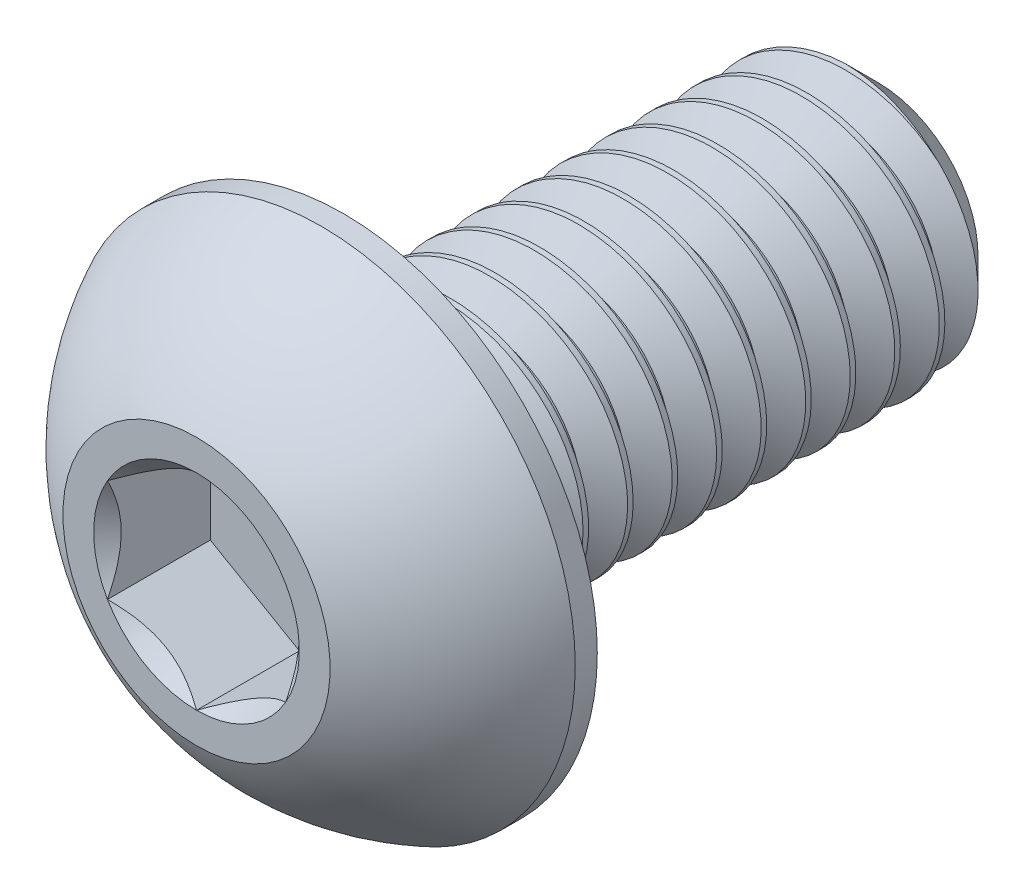
SolidWorks part; units mm, degrees
note: '?' marks a value the reader was unsure of.
ref_plane "Front" through (0, 0, 0) normal (0, 0, 1) x (1, 0, 0)
ref_plane "Top" through (0, 0, 0) normal (0, 1, 0) x (1, 0, 0)
ref_plane "Right" through (0, 0, 0) normal (1, 0, 0) x (0, 0, -1)
sketch "Sketch1" plane through (0, 0, 0) normal (1, 0, 0) x (0, 0, -1)
  line L2 (1.65, 1.5) -> (7.65, 1.5)
  line L3 (7.65, 1.5) -> (7.65, 0)
  line L4 (7.65, 0) -> (1.65, 0)
  line L6 (1.4025, 2.85) -> (1.65, 2.85) construction
  line L7 (7.65, 1.5) -> (7.65, -1.5) construction
  line L8 (0, 0) -> (1.65, 0) construction
  line L9 (1.65, 2.85) -> (1.65, -2.85) construction
  line L11 (1.65, 1.5) -> (1.65, 0)
  line L13 (0, 1) -> (0, -1) construction
  line L14 (0, 1) -> (0, 1.5) construction
  arc A3 (0, 1.5) -> (1.4025, 2.85) centre (2.7948, 0) cw construction
  dimension "D1" = 0.2475
revolve "Revolve1" add sketch "Sketch1" angle 360 mid plane about L4
sketch "Sketch3" plane through (0, 0, -7.65) normal (0, 0, -1) x (-1, 0, 0)
  circle A0 centre (0, 0) radius 1.5
curve "Helix/Spiral1" pitch 0.5 height 6.5 turns 13
chamfer "Chamfer1" distance 0.375 angle 45 1 edges at (0, 1.5, -7.65)
sketch "Sketch7" plane through (0, 0, 0) normal (1, 0, 0) x (0, 0, -1)
  line L6 (1.4025, 2.85) -> (1.65, 2.85) construction
  line L8 (0, 0) -> (1.65, 0) construction
  line L11 (1.65, 2.85) -> (1.65, -2.85) construction
  line L12 (1.4025, 2.85) -> (1.65, 2.85)
  line L13 (0, 0) -> (1.65, 0)
  line L14 (0, 1) -> (0, -1) construction
  line L15 (1.65, 2.85) -> (1.65, 0)
  line L16 (0, 1.5) -> (0, 0)
  arc A2 (1.4025, 2.85) -> (0, 1.5) centre (2.7948, 0) ccw construction
  arc A3 (1.4025, 2.85) -> (0, 1.5) centre (2.7948, 0) ccw
revolve "Revolve2" add sketch "Sketch7" angle 360 mid plane about L13
sketch "Sketch5" plane through (0, 0, 0) normal (0, 0, 1) x (1, 0, 0)
  line L1 (1, -0.5774) -> (1, 0.5774)
  line L2 (1, 0.5774) -> (0, 1.1547)
  line L3 (0, 1.1547) -> (-1, 0.5774)
  line L4 (-1, 0.5774) -> (-1, -0.5774)
  line L5 (-1, -0.5774) -> (0, -1.1547)
  line L6 (0, -1.1547) -> (1, -0.5774)
  circle A0 centre (0, 0) radius 1 construction
extrude "Cut-Extrude2" cut sketch "Sketch5" against normal blind 1.155
sketch "Sketch6" plane through (0, 0, 0) normal (0, 0, 1) x (1, 0, 0)
  circle A0 centre (0, 0) radius 1.1547
extrude "Cut-Extrude3" cut sketch "Sketch6" against normal blind 1.155 draft 45
sketch "Sketch2" plane through (0, 0, 0) normal (1, 0, 0) x (0, 0, -1)
  line L0 (7.275, 1.5) -> (7.7125, 1.5)
  line L1 (7.7125, 1.5) -> (7.525, 1.1752)
  line L2 (7.525, 1.1752) -> (7.4625, 1.1752)
  line L3 (7.4625, 1.1752) -> (7.275, 1.5)
  line L4 (7.3687, 1.3376) -> (7.6187, 1.3376) construction
  dimension "D1" = 60
  dimension "D2" = 0.0625
  dimension "D3" = 0.25
sweep "Cut-Sweep1" cut profiles "Sketch2" path "Helix/Spiral1"
sketch "Sketch10" plane through (0, 0, 0) normal (1, 0, 0) x (0, 0, -1)
  line L0 (7.65, 1.5) -> (7.65, -1.5) construction
  point P0 (6.9, -1.5)
  dimension "D1" = 0.75
ref_axis "Center Axis 1" through (0, 0, -8.1113) along (0, 0, 1)?
ref_plane "Contact Plane 1" through (0, 0, -1.65) normal (0, 0, -1) x (-1, 0, 0)
ref_plane "Contact Plane 2" through (0, 0, 0) normal (0, 0, 1) x (1, 0, 0)
equation "\"D3@Helix/Spiral1\" = \"Lg@Sketch1\" + \"D4@Helix/Spiral1\""
equation "\"D2@Sketch2\" = \"D4@Helix/Spiral1\" * .125"
equation "\"D3@Sketch2\" = \"D4@Helix/Spiral1\" * .5"
equation "\"D1@Chamfer1\" = \"D4@Helix/Spiral1\" * .75"
equation "\"D1@Cut-Extrude2\" = \"Head Ht@Sketch1\" * .7"
equation "\"D1@Sketch1\" = \"Head Ht@Sketch1\" * .15"
equation "\"D1@Sketch10\" = \"D4@Helix/Spiral1\" * 1.5"
equation "\"D1@Cut-Extrude3\" = \"D1@Cut-Extrude2\""
